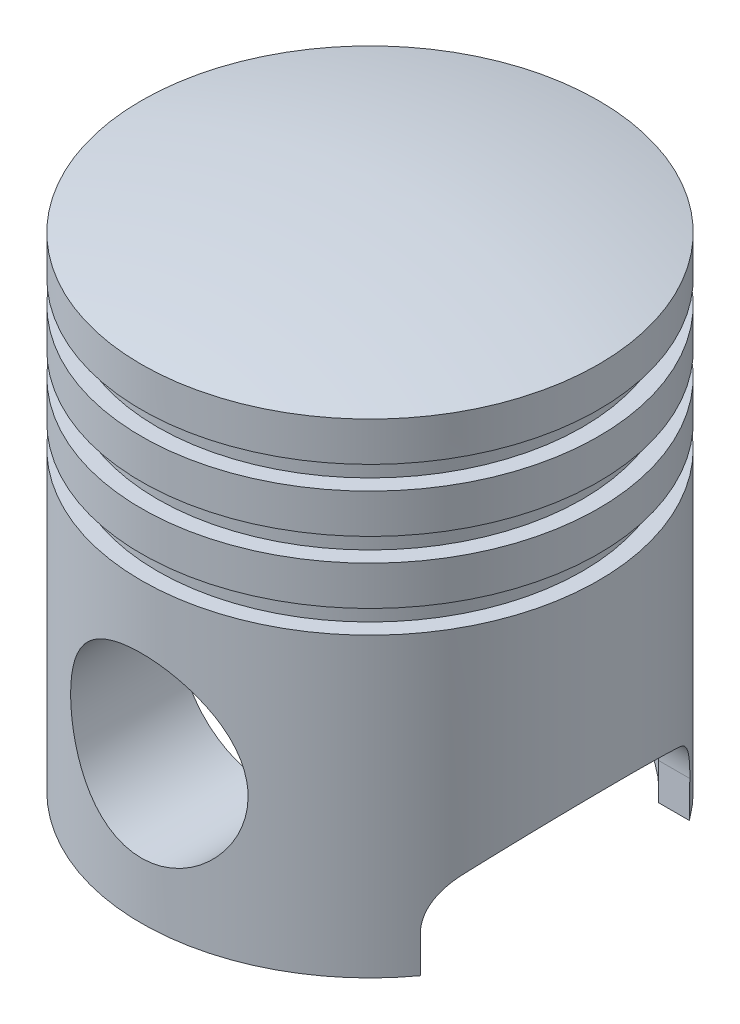
SolidWorks part; units mm, degrees
ref_plane "Front Plane" through (0, 0, 0) normal (0, 0, 1) x (1, 0, 0)
ref_plane "Top Plane" through (0, 0, 0) normal (0, 1, 0) x (1, 0, 0)
ref_plane "Right Plane" through (0, 0, 0) normal (1, 0, 0) x (0, 0, -1)
sketch "Sketch1" plane through (0, 0, 0) normal (0, 1, 0) x (1, 0, 0)
  circle A0 centre (0, 0) radius 42.5
  dimension "D1" = 85
extrude "Boss-Extrude2" add sketch "Sketch1" along normal blind 90
sketch "Sketch2" plane through (0, 90, 0) normal (0, 1, 0) x (1, 0, 0)
  circle A0 centre (0, 0) radius 39.5
  dimension "D1" = 79
extrude "Cut-Extrude4" cut sketch "Sketch2" against normal blind 4.3 from offset 7.3 flip side to cut offset against normal yes
pattern_linear "LPattern1" count 3 spacing 11.6 along (0, -1, 0) of "Cut-Extrude4"
sketch "Sketch5" plane through (0, 0, 0) normal (0, -1, 0) x (-1, 0, 0)
  circle A0 centre (0, 0) radius 38
  dimension "D1" = 76
extrude "Cut-Extrude6" cut sketch "Sketch5" against normal blind 85
dome "Dome1" faces to dome 1 distance 5 reverse direction no elliptical dome no face at (0, 90, 42.5) parameters "D1"=5
sketch "Sketch6" plane through (0, 0, 0) normal (0, 0, 1) x (1, 0, 0)
  line L0 (0, 55.2) -> (0, 0) construction
  circle A0 centre (0, 27) radius 16.5
  dimension "D2" = 33
  dimension "D1" = 27
extrude "Cut-Extrude7" cut sketch "Sketch6" against normal through all both and the other way through all contours A0
sketch "Sketch7" plane through (0, 0, 0) normal (1, 0, 0) x (0, 0, -1)
  line L0 (-25, 0) -> (-25, 12)
  line L1 (-25, 0) -> (25, 0)
  line L2 (25, 0) -> (25.6639, 12)
  arc A0 (-25, 12) -> (25.6639, 12) centre (0.3319, -18.9563) cw
  dimension "D1" = 50
  dimension "D2" = 25
  dimension "D3" = 25
sketch "Sketch8" plane through (0, 0, 0) normal (1, 0, 0) x (0, 0, -1)
  arc A0 (-25, 12) -> (25.6639, 12) centre (0.3319, -47.121) cw
sketch "Sketch9" plane through (0, 0, 0) normal (1, 0, 0) x (0, 0, -1)
extrude "Cut-Extrude8" cut sketch "Sketch7" against normal through all both and the other way through all
fillet "Fillet1" radius 10 4 edges at (-31.4937, 12, 25) (31.4937, 12, 25) (30.9504, 12, -25.6639) (-30.9504, 12, -25.6639)
sketch "Sketch10" plane through (0, 0, 0) normal (0, 0, 1) x (1, 0, 0)
  circle A0 centre (0, 27) radius 16.5 construction
  circle A1 centre (0, 27) radius 16.5
sketch "Sketch11" plane through (0, 0, 0) normal (0, 0, 1) x (1, 0, 0)
  circle A0 centre (0, 27) radius 16.5 construction
  circle A1 centre (0, 27) radius 16.5
  circle A2 centre (0, 27) radius 22.5
  dimension "D1" = 45
extrude "Boss-Extrude3" add sketch "Sketch11" along normal up to next from offset 19
mirror "Mirror1" about plane through (0, 0, 0) normal (0, 0, 1) of "Boss-Extrude3"
